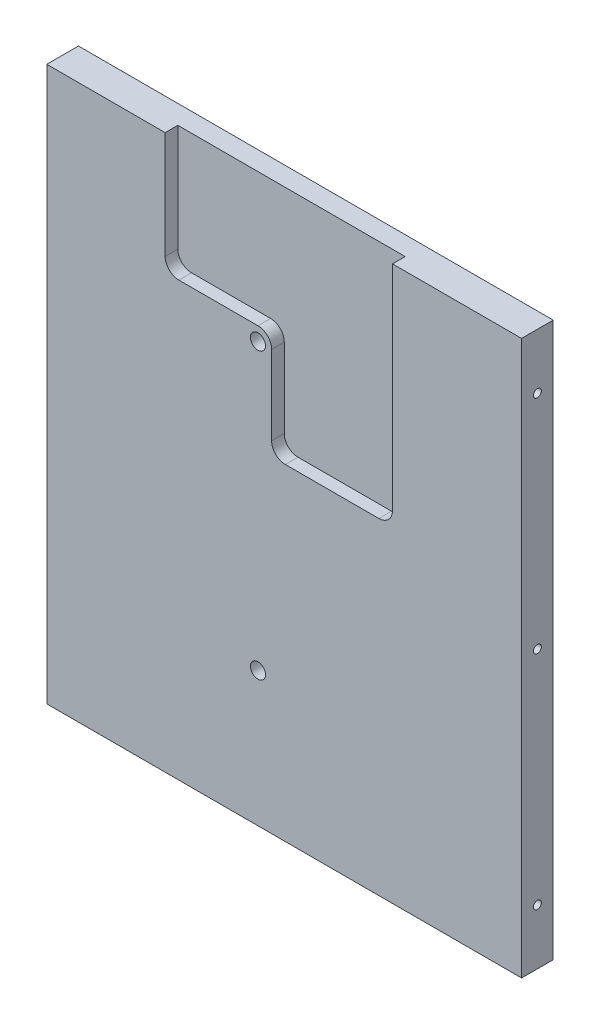
SolidWorks part; units mm, degrees
ref_plane "Ebene vorne" through (0, 0, 0) normal (0, 0, 1) x (1, 0, 0)
ref_plane "Ebene oben" through (0, 0, 0) normal (0, 1, 0) x (1, 0, 0)
ref_plane "Ebene rechts" through (0, 0, 0) normal (1, 0, 0) x (0, 0, -1)
sketch "Skizze1" plane through (0, 0, 0) normal (0, 0, 1) x (1, 0, 0)
  line L1 (-96.1409, 69.4002) -> (53.8591, 69.4002)
  line L2 (-96.1409, 69.4002) -> (-96.1409, -105.5998)
  line L3 (-96.1409, -105.5998) -> (53.8591, -105.5998)
  line L4 (53.8591, 69.4002) -> (53.8591, -105.5998)
  dimension "D1" = 150
  dimension "D2" = 175
extrude "Aufsatz-Linear austragen1" add sketch "Skizze1" along normal blind 10
sketch "Skizze2" plane through (0, 0, 10) normal (0, 0, 1) x (1, 0, 0)
  line L0 (-96.1409, -18.0998) -> (53.8591, -18.0998) construction
  line L1 (-96.1409, 69.4002) -> (-96.1409, -105.5998) construction
  line L2 (-96.1409, -18.0998) -> (33.5831, 69.4002) construction
  line L3 (53.8591, 69.4002) -> (-96.1409, 69.4002) construction
  line L4 (-96.1409, -18.0998) -> (33.5831, -105.5998) construction
  line L5 (-96.1409, -105.5998) -> (53.8591, -105.5998) construction
  line L6 (-29.4257, 26.9002) -> (53.8591, 26.9002) construction
  line L11 (53.8591, -105.5998) -> (53.8591, 69.4002) construction
  line L12 (-29.4257, -63.0998) -> (-29.4257, 26.9002) construction
  line L13 (53.8591, -8.0998) -> (-96.1409, -8.0998) construction
  line L14 (53.8591, -28.0998) -> (-96.1409, -28.0998) construction
  line L15 (-21.1409, -28.0998) -> (-21.1409, -8.0998) construction
  circle A0 centre (-29.4257, 26.9002) radius 2.3876
  circle A1 centre (-29.4257, -63.0998) radius 2.3876
  point P29 (-21.1409, -18.0998)
  dimension "D4" = 4.7752
  dimension "D6" = 4.7752
  dimension "D1" = 34
  dimension "D2" = 34
  dimension "D3" = 90
  dimension "D10" = 20
extrude "Schnitt-Linear austragen1" cut sketch "Skizze2" against normal blind 10
sketch "Skizze3" plane through (0, 0, 10) normal (0, 0, 1) x (1, 0, 0)
  line L1 (-54.4257, 31.2182) -> (-54.4257, 69.4002) construction
  line L7 (-54.4257, 31.2182) -> (-29.4257, 31.2182)
  line L8 (-25.1077, 26.9002) -> (-25.1077, 1.9002)
  line L9 (-20.7897, -2.4178) -> (8.7563, -2.4178)
  line L10 (13.0743, 1.9002) -> (13.0743, 69.4002)
  line L11 (53.8591, 69.4002) -> (-96.1409, 69.4002) construction
  line L12 (-58.7437, 35.5362) -> (-58.7437, 69.4002)
  line L13 (-58.7437, 69.4002) -> (13.0743, 69.4002)
  line L14 (-25.1077, 1.9002) -> (13.0743, 1.9002) construction
  arc A3 (-29.4257, 31.2182) -> (-25.1077, 26.9002) centre (-29.4257, 26.9002) cw
  arc A4 (-25.1077, 1.9002) -> (-20.7897, -2.4178) centre (-20.7897, 1.9002) ccw
  arc A5 (8.7563, -2.4178) -> (13.0743, 1.9002) centre (8.7563, 1.9002) ccw
  arc A6 (-54.4257, 31.2182) -> (-58.7437, 35.5362) centre (-54.4257, 35.5362) cw
  circle A7 centre (-29.4257, 26.9002) radius 2.3876 construction
  dimension "D1" = 4.318
  dimension "D2" = 25
  dimension "D3" = 25
extrude "Schnitt-Linear austragen2" cut sketch "Skizze3" against normal blind 4
sketch "Skizze4" plane through (-96.1409, 0, 0) normal (-1, 0, 0) x (0, 0, 1)
  line L0 (0, -18.0998) -> (10, -18.0998) construction
  line L1 (5, -88.0998) -> (5, -18.0998) construction
  line L2 (5, -18.0998) -> (5, 51.9002) construction
  line L4 (10, 69.4002) -> (10, -105.5998) construction
  line L5 (0, 69.4002) -> (0, -105.5998) construction
  circle A0 centre (5, 51.9002) radius 1.25
  circle A1 centre (5, -18.0998) radius 1.25
  circle A3 centre (5, -88.0998) radius 1.25
  point P7 (5, -18.0998)
  dimension "D2" = 2.5
  dimension "D1" = 70
extrude "Schnitt-Linear austragen3" cut sketch "Skizze4" against normal blind 5
sketch "Skizze6" plane through (53.8591, 0, 0) normal (1, 0, 0) x (0, 0, -1)
  line L0 (-10, -18.0998) -> (0, -18.0998) construction
  line L1 (-5, -88.0998) -> (-5, -18.0998) construction
  line L2 (-5, -18.0998) -> (-5, 51.9002) construction
  line L4 (0, -105.5998) -> (0, 69.4002) construction
  line L5 (-10, -105.5998) -> (-10, 69.4002) construction
  circle A0 centre (-5, 51.9002) radius 1.25
  circle A1 centre (-5, -18.0998) radius 1.25
  circle A3 centre (-5, -88.0998) radius 1.25
  point P2 (-5, -18.0998)
  point P7 (-5, -18.0998)
  dimension "D2" = 2.5
  dimension "D1" = 70
extrude "Schnitt-Linear austragen4" cut sketch "Skizze6" against normal blind 5
